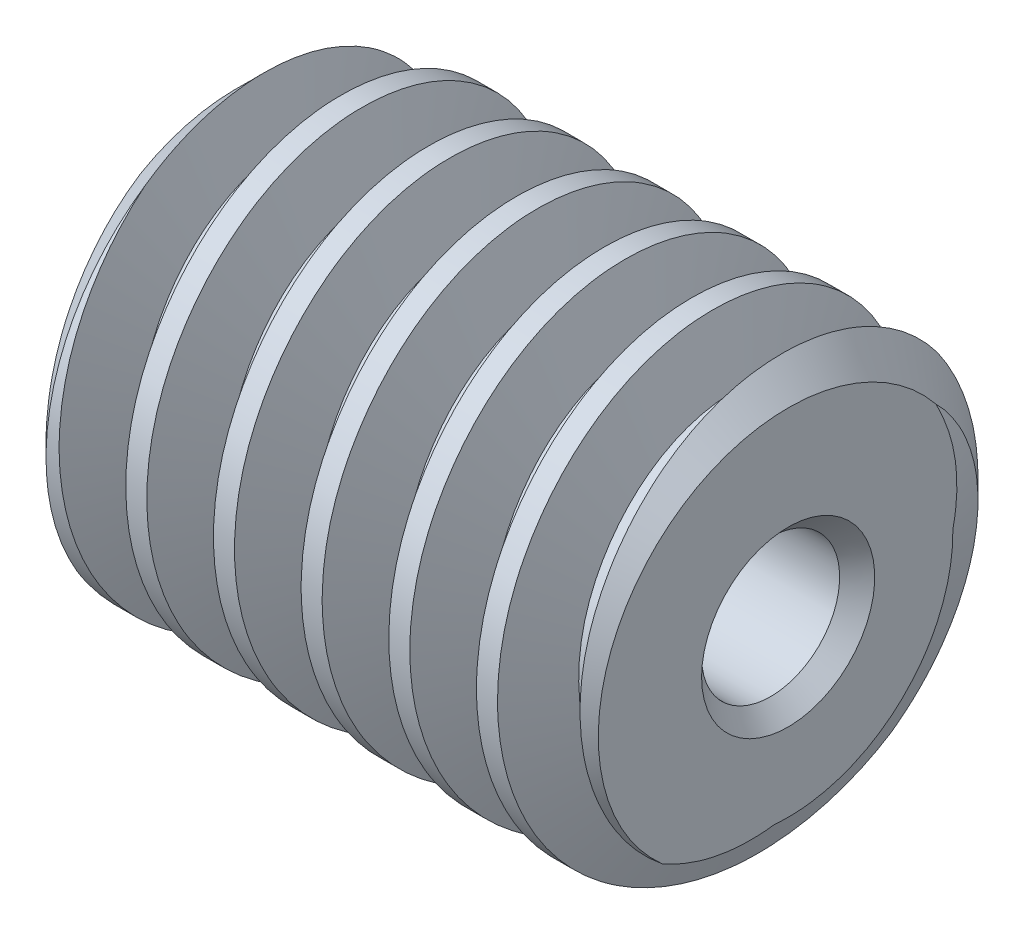
SolidWorks part; units mm, degrees
ref_plane "Front Plane" through (0, 0, 0) normal (0, 0, 1) x (1, 0, 0)
ref_plane "Top Plane" through (0, 0, 0) normal (0, 1, 0) x (1, 0, 0)
ref_plane "Right Plane" through (0, 0, 0) normal (1, 0, 0) x (0, 0, -1)
sketch "Sketch1" plane through (0, 0, 0) normal (0, 0, 1) x (1, 0, 0)
  line L0 (-53.1103, 0) -> (49946.8897, 0) construction
  line L1 (55, 0) -> (-55, 0) construction
  line L2 (-0.127, 0.5) -> (-3.873, 0.5)
  line L3 (0, -55) -> (0, 55) construction
  line L4 (-3.873, 0.5) -> (-4, 0.627)
  line L5 (-4, 0.627) -> (-4, 1.375)
  line L6 (-4, 1.375) -> (-3.75, 1.625)
  line L7 (-3.75, 1.625) -> (-0.25, 1.625)
  line L8 (-0.25, 1.625) -> (0, 1.375)
  line L9 (0, 1.375) -> (0, 0.627)
  line L10 (0, 0.627) -> (-0.127, 0.5)
  dimension "D1" = 1
  dimension "D2" = 45
  dimension "D3" = 3.25
  dimension "D4" = 4
  dimension "D5" = 0.25
  dimension "D6" = 0.127
revolve "Revolve1" add sketch "Sketch1" angle 360 about L0
sketch "Sketch2" plane through (0, 0, 0) normal (1, 0, 0) x (0, 0, -1)
  circle A0 centre (0, 0) radius 1.625 construction
  circle A1 centre (0, 0) radius 1.625
curve "Helix/Spiral1" pitch 0.635 height 4.445 radius 1.625 centre (0, 0, 0) axis (-1, 0, 0) start towards (0, 1, 0)
sketch "Sketch4" plane through (0, 0, 0) normal (0, 0, 1) x (1, 0, 0)
  line L0 (0, 1.625) -> (0.1572, 1.1932)
  line L1 (0, -55) -> (0, 55) construction
  line L2 (0.1572, 1.1932) -> (0.3254, 1.1932)
  line L3 (0.3254, 1.1932) -> (0.4826, 1.625)
  line L4 (0.4826, 1.625) -> (0, 1.625)
  line L5 (0.2413, 0.692) -> (0.2413, 50000.692) construction
  spline S0 degree 3 poles (0, 1.625) (-0.0131, 1.625) (-0.0397, 1.5404) (-0.0794, 1.179) (-0.1323, 0.4577) (-0.1852, -0.4577) (-0.2381, -1.179) (-0.2778, -1.5404) (-0.3175, -1.6673) (-0.3572, -1.5404) (-0.3969, -1.179) (-0.4498, -0.4577) (-0.5027, 0.4577) (-0.5556, 1.179) (-0.5953, 1.5404) (-0.635, 1.6673) (-0.6747, 1.5404) (-0.7144, 1.179) (-0.7673, 0.4577) (-0.8202, -0.4577) (-0.8731, -1.179) (-0.9128, -1.5404) (-0.9525, -1.6673) (-0.9922, -1.5404) (-1.0319, -1.179) (-1.0848, -0.4577) (-1.1377, 0.4577) (-1.1906, 1.179) (-1.2303, 1.5404) (-1.27, 1.6673) (-1.3097, 1.5404) (-1.3494, 1.179) (-1.4023, 0.4577) (-1.4552, -0.4577) (-1.5081, -1.179) (-1.5478, -1.5404) (-1.5875, -1.6673) (-1.6272, -1.5404) (-1.6669, -1.179) (-1.7198, -0.4577) (-1.7727, 0.4577) (-1.8256, 1.179) (-1.8653, 1.5404) (-1.905, 1.6673) (-1.9447, 1.5404) (-1.9844, 1.179) (-2.0373, 0.4577) (-2.0902, -0.4577) (-2.1431, -1.179) (-2.1828, -1.5404) (-2.2225, -1.6673) (-2.2622, -1.5404) (-2.3019, -1.179) (-2.3548, -0.4577) (-2.4077, 0.4577) (-2.4606, 1.179) (-2.5003, 1.5404) (-2.54, 1.6673) (-2.5797, 1.5404) (-2.6194, 1.179) (-2.6723, 0.4577) (-2.7252, -0.4577) (-2.7781, -1.179) (-2.8178, -1.5404) (-2.8575, -1.6673) (-2.8972, -1.5404) (-2.9369, -1.179) (-2.9898, -0.4577) (-3.0427, 0.4577) (-3.0956, 1.179) (-3.1353, 1.5404) (-3.175, 1.6673) (-3.2147, 1.5404) (-3.2544, 1.179) (-3.3073, 0.4577) (-3.3602, -0.4577) (-3.4131, -1.179) (-3.4528, -1.5404) (-3.4925, -1.6673) (-3.5322, -1.5404) (-3.5719, -1.179) (-3.6248, -0.4577) (-3.6777, 0.4577) (-3.7306, 1.179) (-3.7703, 1.5404) (-3.81, 1.6673) (-3.8497, 1.5404) (-3.8894, 1.179) (-3.9423, 0.4577) (-3.9952, -0.4577) (-4.0481, -1.179) (-4.0878, -1.5404) (-4.1275, -1.6673) (-4.1672, -1.5404) (-4.2069, -1.179) (-4.2598, -0.4577) (-4.3127, 0.4577) (-4.3656, 1.179) (-4.4053, 1.5404) (-4.4319, 1.625) (-4.445, 1.625) knots 0 0 0 0 0.008929 0.017857 0.026786 0.044643 0.053571 0.0625 0.071429 0.080357 0.089286 0.098214 0.116071 0.125 0.133929 0.142857 0.151786 0.160714 0.169643 0.1875 0.196429 0.205357 0.214286 0.223214 0.232143 0.241071 0.258929 0.267857 0.276786 0.285714 0.294643 0.303571 0.3125 0.330357 0.339286 0.348214 0.357143 0.366071 0.375 0.383929 0.401786 0.410714 0.419643 0.428571 0.4375 0.446429 0.455357 0.473214 0.482143 0.491071 0.5 0.508929 0.517857 0.526786 0.544643 0.553571 0.5625 0.571429 0.580357 0.589286 0.598214 0.616071 0.625 0.633929 0.642857 0.651786 0.660714 0.669643 0.6875 0.696429 0.705357 0.714286 0.723214 0.732143 0.741071 0.758929 0.767857 0.776786 0.785714 0.794643 0.803571 0.8125 0.830357 0.839286 0.848214 0.857143 0.866071 0.875 0.883929 0.901786 0.910714 0.919643 0.928571 0.9375 0.946429 0.955357 0.973214 0.982143 0.991071 1 1 1 1 construction
  point P6 (0.2413, 1.1932)
  point P9 (0.2413, 1.625)
  dimension "D1" = 20
  dimension "D2" = 0.4826
  dimension "D3" = 0.4318
sweep "Cut-Sweep1" cut profiles "Sketch4" path "Helix/Spiral1" align with end faces yes
